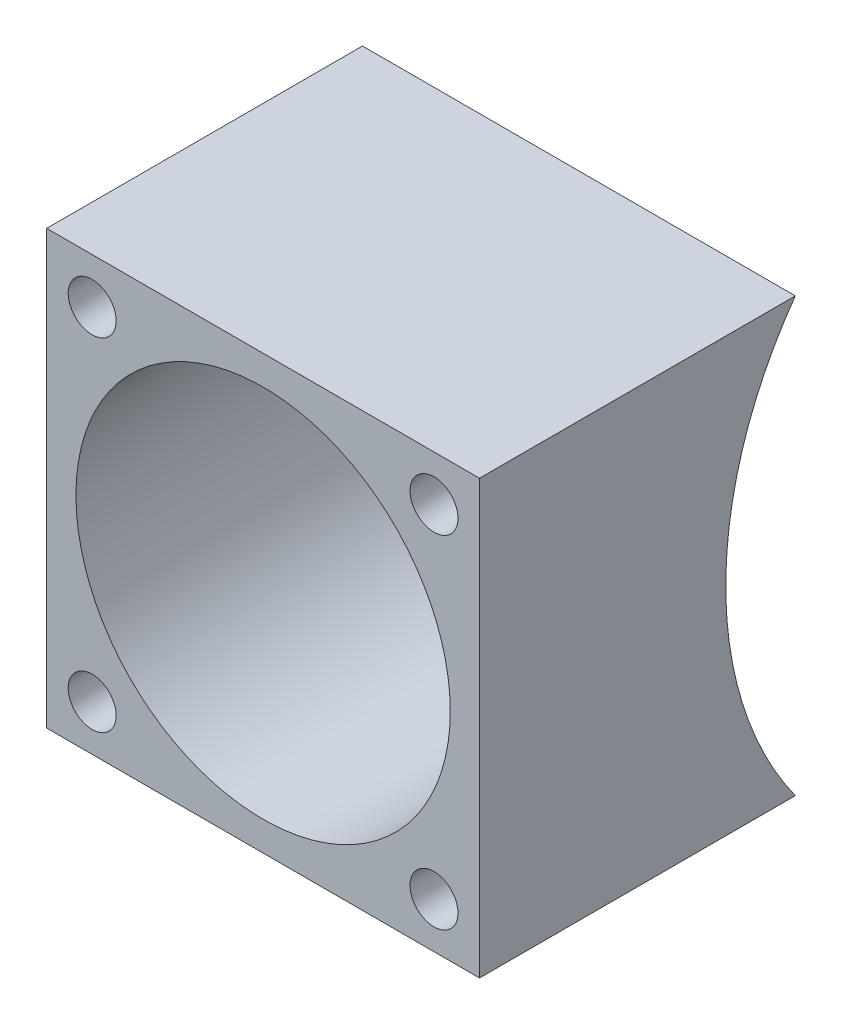
SolidWorks part; units mm, degrees
ref_plane "Front Plane" through (0, 0, 0) normal (0, 0, 1) x (1, 0, 0)
ref_plane "Top Plane" through (0, 0, 0) normal (0, 1, 0) x (1, 0, 0)
ref_plane "Right Plane" through (0, 0, 0) normal (1, 0, 0) x (0, 0, -1)
sketch "Sketch1" plane through (0, 0, 0) normal (0, 0, 1) x (1, 0, 0)
  line L1 (-18.5, 18.5) -> (18.5, 18.5)
  line L2 (-18.5, 18.5) -> (-18.5, -18.5)
  line L3 (-18.5, -18.5) -> (18.5, -18.5)
  line L4 (18.5, 18.5) -> (18.5, -18.5)
  line L5 (-18.5, 18.5) -> (18.5, -18.5) construction
  line L6 (-18.5, -18.5) -> (18.5, 18.5) construction
  point P0 (0, 0)
  dimension "D1" = 37
  dimension "D2" = 37
extrude "Boss-Extrude1" add sketch "Sketch1" along normal blind 52.8
sketch "Sketch2" plane through (0, 0, 0) normal (1, 0, 0) x (0, 0, -1)
  circle A0 centre (0, 0) radius 31.75
  dimension "D1" = 63.5
extrude "Cut-Extrude1" cut sketch "Sketch2" against normal blind 20 and the other way blind 20
sketch "Sketch5" plane through (0, 0, 0) normal (0, 0, 1) x (1, 0, 0)
  circle A0 centre (0, 0) radius 16
  dimension "D1" = 32
extrude "Cut-Extrude2" cut sketch "Sketch5" along normal through all
sketch "Sketch6" plane through (0, 0, 52.8) normal (0, 0, 1) x (1, 0, 0)
  line L0 (-18.5, 18.5) -> (18.5, -18.5) construction
  line L1 (18.5, -18.5) -> (-18.5, -18.5) construction
  line L2 (-18.5, -18.5) -> (18.5, 18.5) construction
  circle A1 centre (-14.6109, -14.6109) radius 2.05
  circle A2 centre (14.6109, -14.6109) radius 2.05
  circle A3 centre (14.6109, 14.6109) radius 2.05
  circle A4 centre (-14.6109, 14.6109) radius 2.05
  point P4 (-14.6109, 14.6109)
  point P9 (14.6109, 14.6109)
  point P10 (-14.6109, -14.6109)
  point P11 (14.6109, -14.6109)
  dimension "D5" = 4.1
  dimension "D6" = 4.1
  dimension "D7" = 4.1
  dimension "D8" = 4.1
  dimension "D1" = 5.5
  dimension "D2" = 5.5
  dimension "D3" = 5.5
  dimension "D4" = 5.5
extrude "Cut-Extrude3" cut sketch "Sketch6" against normal through all
